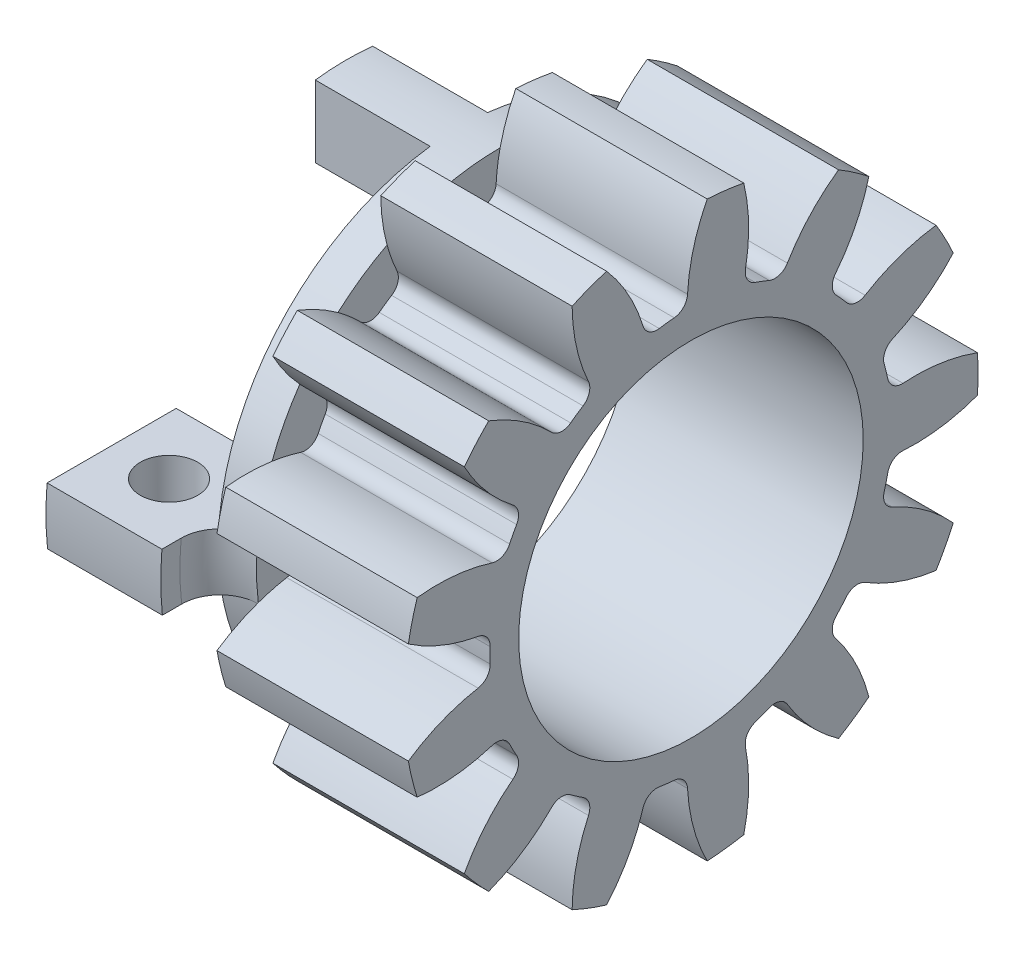
SolidWorks part; units mm, degrees
ref_plane "Front Plane" through (0, 0, 0) normal (1, 0, 0) x (0, 1, 0)
ref_plane "Top Plane" through (0, 0, 0) normal (0, 0, 1) x (0, 1, 0)
ref_plane "Right Plane" through (0, 0, 0) normal (0, 1, 0) x (-1, 0, 0)
sketch "Sketch1" plane through (0, 0, 0) normal (1, 0, 0) x (0, 1, 0)
  circle A0 centre (0, 0) radius 15
  dimension "D1" = 30
extrude "Boss-Extrude1" add sketch "Sketch1" along normal blind 10
sketch "Sketch2" plane through (10, 0, 0) normal (1, 0, 0) x (0, 1, 0)
  line L0 (0, 0) -> (0, 15) construction
  line L1 (0, 0) -> (-1.0758, 10.4447) construction
  line L2 (0, 8.3214) -> (-2.9222, 16.35) construction
  arc A0 (1.0758, 10.4447) -> (-1.0758, 10.4447) centre (0, 0) ccw
  arc A1 (1.6662, 12.8928) -> (-1.6662, 12.8928) centre (0, 0) ccw construction
  arc A2 (2.648, 14.7644) -> (-2.648, 14.7644) centre (0, 0) ccw
  arc A3 (-1.0758, 10.4447) -> (-2.648, 14.7644) centre (-10.4481, 9.4794) ccw
  arc A4 (1.0758, 10.4447) -> (2.648, 14.7644) centre (10.4481, 9.4794) cw
  circle A5 centre (0, 0) radius 15 construction
  point P14 (-1.5944, 12.7019)
  dimension "D1" = 30
  dimension "D2" = 26
  dimension "D3" = 4.5
  dimension "D4" = 20
  dimension "D5" = 3.3416
extrude "Cut-Extrude1" cut sketch "Sketch2" against normal through all
fillet "Fillet1" radius 0.76 2 edges at (5, 1.0758, 10.4447) (5, -1.0758, 10.4447)
pattern_circular "CirPattern1" count 13 over 360 about axis through (10, 0, 0) along (1, 0, 0) of "Cut-Extrude1", "Fillet1"
sketch "Sketch3" plane through (10, 0, 0) normal (1, 0, 0) x (0, 1, 0)
  line L0 (2, -1.5) -> (2, 1.5)
  arc A0 (2, 1.5) -> (2, -1.5) centre (0, 0) ccw
  dimension "D1" = 2.5
  dimension "D2" = 2
extrude "Cut-Extrude2" cut sketch "Sketch3" against normal through all
sketch "Sketch4" [suppressed] plane through (10, 0, 0) normal (1, 0, 0) x (0, 1, 0)
  line L0 (-32, 0) -> (32, 0)
  circle A0 centre (0, 0) radius 32 construction
  arc A1 (-32, 0) -> (32, 0) centre (0, 0) ccw
  point P7 (0, 0)
extrude "Cut-Extrude3" [suppressed] cut sketch "Sketch4" against normal through all
ref_plane "Plane1" [suppressed] through (0, 0, 2) normal (0, 0, -1) x (-1, 0, 0)
sketch "Sketch8" [suppressed] plane through (0, 0, 2) normal (0, 0, -1) x (-1, 0, 0)
  line L0 (-5, 32) -> (-5, -32) construction
  line L1 (0, 32) -> (-10, 32) construction
  line L2 (0, -32) -> (-10, -32) construction
  line L3 (0, 0) -> (-10, 0) construction
  line L4 (-3.3546, 5.15) -> (-1.7091, 8)
  line L5 (-1.7091, 8) -> (-3.3546, 10.85)
  line L6 (-3.3546, 10.85) -> (-6.6454, 10.85)
  line L7 (-6.6454, 10.85) -> (-8.2909, 8) construction
  line L8 (-8.2909, 8) -> (-6.6454, 5.15) construction
  line L9 (-6.6454, 5.15) -> (-3.3546, 5.15)
  line L10 (-10, 32) -> (-10, -32) construction
  line L11 (-6.6454, 5.15) -> (-10, 5.15)
  line L12 (-10, 5.15) -> (-10, 10.85)
  line L13 (-10, 10.85) -> (-6.6454, 10.85)
  line L14 (-8.2909, -8) -> (-6.6454, -5.15) construction
  line L15 (-6.6454, -10.85) -> (-8.2909, -8) construction
  line L16 (-10, -10.85) -> (-6.6454, -10.85)
  line L17 (-10, -5.15) -> (-10, -10.85)
  line L18 (-6.6454, -5.15) -> (-10, -5.15)
  line L19 (-6.6454, -5.15) -> (-3.3546, -5.15)
  line L20 (-3.3546, -10.85) -> (-6.6454, -10.85)
  line L21 (-1.7091, -8) -> (-3.3546, -10.85)
  line L22 (-3.3546, -5.15) -> (-1.7091, -8)
  circle A0 centre (-5, 8) radius 2.85 construction
  circle A1 centre (-5, -8) radius 2.85 construction
  dimension "D1" = 5.7
  dimension "D2" = 16
extrude "Cut-Extrude6" [suppressed] cut sketch "Sketch8" against normal blind 2.6
sketch "Sketch9" [suppressed] plane through (0, 0, 0) normal (0, 0, -1) x (1, 0, 0)
  line L0 (5, 32) -> (5, -32) construction
  line L1 (0, 32) -> (10, 32) construction
  line L2 (0, -32) -> (10, -32) construction
  line L3 (0, 0) -> (10, 0) construction
  line L4 (10, -32) -> (10, 32) construction
  line L5 (1.7091, 8) -> (3.3546, 5.15)
  line L6 (3.3546, 10.85) -> (1.7091, 8)
  line L7 (10, 10.85) -> (3.3546, 10.85)
  line L8 (10, 5.15) -> (10, 10.85)
  line L9 (3.3546, 5.15) -> (10, 5.15)
  line L10 (1.7091, 8) -> (3.3546, 5.15) construction
  line L11 (3.3546, 10.85) -> (1.7091, 8) construction
  line L12 (10, 10.85) -> (3.3546, 10.85) construction
  line L13 (10, 5.15) -> (10, 10.85) construction
  line L14 (3.3546, 5.15) -> (10, 5.15) construction
  line L15 (3.3546, -5.15) -> (10, -5.15) construction
  line L16 (10, -5.15) -> (10, -10.85) construction
  line L17 (10, -10.85) -> (3.3546, -10.85) construction
  line L18 (3.3546, -10.85) -> (1.7091, -8) construction
  line L19 (1.7091, -8) -> (3.3546, -5.15) construction
  circle A0 centre (5, 8) radius 1.75
  circle A1 centre (5, -8) radius 1.75
  dimension "D2" = 3.5
  dimension "D1" = 0
extrude "Cut-Extrude7" [suppressed] cut sketch "Sketch9" against normal blind 11
sketch "Sketch12" plane through (10, 0, 0) normal (1, 0, 0) x (0, 1, 0)
  circle A0 centre (0, 0) radius 9
  dimension "D1" = 18
extrude "Cut-Extrude8" cut sketch "Sketch12" against normal through all and the other way through all
sketch "Sketch17" plane through (0, 0, 0) normal (-1, 0, 0) x (0, -1, 0)
  circle A0 centre (0, 0) radius 8
  circle A2 centre (0, 0) radius 12.7
  dimension "D1" = 25.4
extrude "Boss-Extrude3" [suppressed] add sketch "Sketch17" along normal blind 1
sketch "Sketch22" plane through (0, 0, 0) normal (-1, 0, 0) x (0, -1, 0)
  circle A0 centre (0, 0) radius 12.7
  circle A1 centre (0, 0) radius 9 construction
  circle A2 centre (0, 0) radius 9
  dimension "D1" = 25.4
extrude "Boss-Extrude6" add sketch "Sketch22" along normal blind 2
sketch "Sketch18" plane through (-2, 0, 0) normal (-1, 0, 0) x (0, -1, 0)
  line L13 (-1.625, -8.8521) -> (-1.625, -15.6157)
  line L14 (1.375, -8.8943) -> (1.375, -15.6397)
  line L15 (-8.8521, 1.625) -> (-15.6157, 1.625)
  line L16 (-8.8943, -1.375) -> (-15.6397, -1.375)
  line L17 (1.625, 8.8521) -> (1.625, 15.6157)
  line L18 (-1.375, 8.8943) -> (-1.375, 15.6397)
  line L19 (8.8521, -1.625) -> (15.6157, -1.625)
  line L20 (8.8943, 1.375) -> (15.6397, 1.375)
  line L23 (0, -9) -> (0, -12.7) construction
  arc A12 (-1.625, -15.6157) -> (1.375, -15.6397) centre (0, 0) ccw
  arc A13 (-15.6157, 1.625) -> (-15.6397, -1.375) centre (0, 0) ccw
  arc A14 (-8.8521, 1.625) -> (-8.8943, -1.375) centre (0, 0) ccw
  arc A15 (1.625, 15.6157) -> (-1.375, 15.6397) centre (0, 0) ccw
  arc A16 (1.625, 8.8521) -> (-1.375, 8.8943) centre (0, 0) ccw
  arc A17 (15.6157, -1.625) -> (15.6397, 1.375) centre (0, 0) ccw
  arc A18 (8.8521, -1.625) -> (8.8943, 1.375) centre (0, 0) ccw
  arc A21 (-1.5023, -12.6108) -> (1.5023, -12.6108) centre (0, 0) ccw construction
  circle A22 centre (0, 0) radius 9 construction
  circle A23 centre (0, 0) radius 9 construction
  arc A25 (-1.625, -8.8521) -> (1.375, -8.8943) centre (0, 0) ccw
  point P29 (0, 0)
  dimension "D1" = 3
  dimension "D2" = 4
  dimension "D3" = 3
extrude "Boss-Extrude4" add sketch "Sketch18" along normal blind 6
sketch "Sketch26" plane through (0, 1.375, 0) normal (0, 1, 0) x (-1, 0, 0)
  line L0 (5, 12.267) -> (5, 8.8943) construction
  line L1 (8, -8.8521) -> (8, 8.8943) construction
  line L3 (8, 0.0211) -> (1.4708, 0.0211) construction
  line L5 (2, 8.8943) -> (2, 15.6397) construction
  line L6 (8, 12.267) -> (2, 12.267) construction
  line L10 (8, 8.8943) -> (2, 8.8943) construction
  circle A0 centre (5, 12.267) radius 1.5
  circle A1 centre (5, -12.2247) radius 1.5
  point P9 (-1.4351, 12.7796)
  point P10 (0, 0)
  dimension "D1" = 3
extrude "Cut-Extrude17" cut sketch "Sketch26" against normal through all both and the other way through all
sketch "Sketch27" plane through (-8, 0, 0) normal (-1, 0, 0) x (0, -1, 0)
  line L0 (12.5956, -1.625) -> (17.7781, -1.625)
  line L1 (17.7781, -1.625) -> (17.7781, 1.375)
  line L2 (17.7781, 1.375) -> (12.6253, 1.375)
  line L3 (-12.5956, 1.625) -> (-17.5497, 1.625)
  line L4 (-17.5497, 1.625) -> (-17.5497, -1.375)
  line L5 (-17.5497, -1.375) -> (-12.6253, -1.375)
  arc A0 (12.5956, -1.625) -> (12.6253, 1.375) centre (0, 0) ccw construction
  arc A1 (-12.5956, 1.625) -> (-12.6253, -1.375) centre (0, 0) ccw construction
  arc A2 (12.5956, -1.625) -> (12.6253, 1.375) centre (0, 0) ccw
  arc A3 (-12.5956, 1.625) -> (-12.6253, -1.375) centre (0, 0) ccw
extrude "Cut-Extrude18" cut sketch "Sketch27" against normal up to next
fillet "Fillet2" radius 2 2 edges at (-2, -0.1259, 12.6994) (-2, 0.1259, -12.6994)
equation "\"No. of Teeth\"= 13"
equation "\"Module\"= 2"
equation "\"Bore Diameter\"= 5"
equation "\"Pressure Angle\"= 20"
equation "\"Outer Diameter\"= ( \"No. of Teeth\" + 2 ) * \"Module\""
equation "\"Pitch Diameter\"= ( \"No. of Teeth\" * \"Module\" )"
equation "\"Backlash\"= 0.1 * \"Module\""
equation "\"Arc Length\"= ( ( \"Module\" * pi ) / 2 ) + \"Backlash\""
equation "\"Filet Radius\"= 0.38 * \"Module\""
equation "\"Tooth Depth\"= IIF ( \"Module\" <= 1.25 , \"Module\" * 2.4 , \"Module\" * 2.25 )"
equation "\"D1@Fillet1\"=\"Filet Radius\""
equation "\"D1@CirPattern1\"=\"No. of Teeth\""
equation "\"D1@Sketch1\"=\"Outer Diameter\""
equation "\"D5@Sketch2\"=\"Arc Length\""
equation "\"D4@Sketch2\"=\"Pressure Angle\""
equation "\"D2@Sketch2\"=\"Pitch Diameter\""
equation "\"D1@Sketch2\"=\"Outer Diameter\""
equation "\"D3@Sketch2\"= \"Tooth Depth\""
